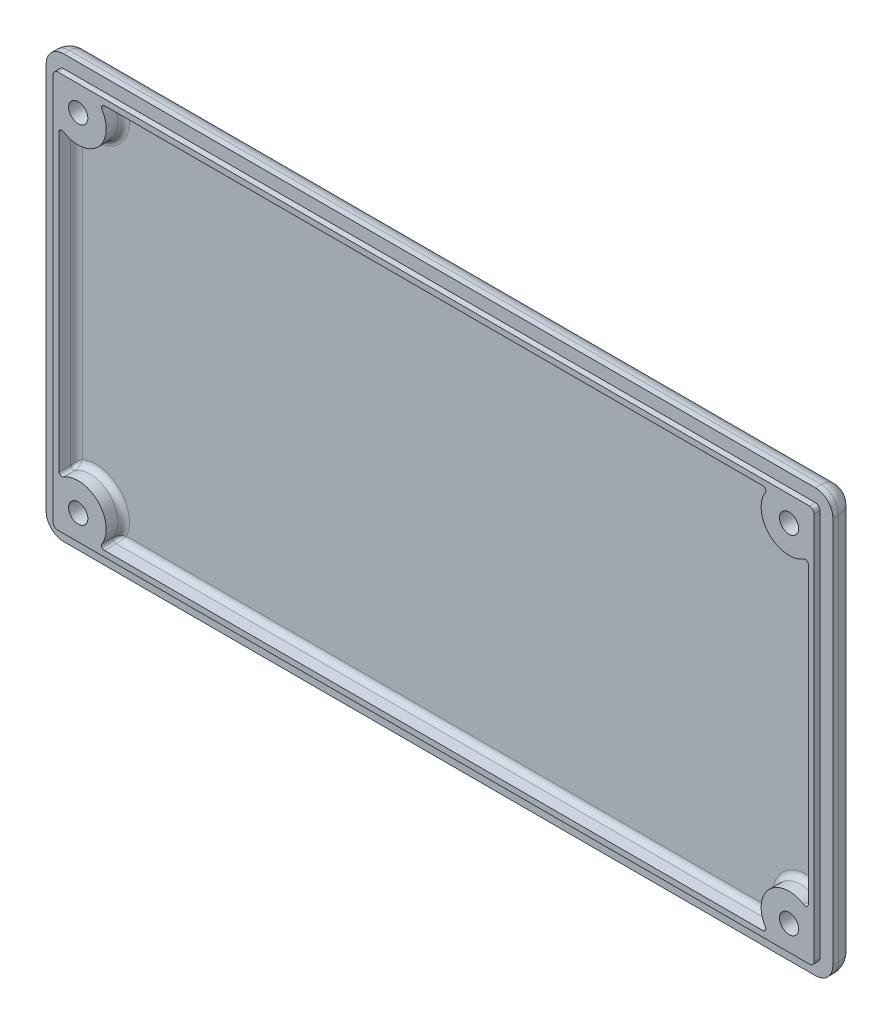
SolidWorks part; units mm, degrees
ref_plane "Front Plane" through (0, 0, 0) normal (0, 0, 1) x (1, 0, 0)
ref_plane "Top Plane" through (0, 0, 0) normal (0, 1, 0) x (1, 0, 0)
ref_plane "Right Plane" through (0, 0, 0) normal (1, 0, 0) x (0, 0, -1)
sketch "Sketch1" plane through (0, 0, 0) normal (0, 0, 1) x (1, 0, 0)
  line L0 (3, 0) -> (132, 0)
  line L1 (0, 3) -> (0, 69.5)
  line L2 (3, 72.5) -> (132, 72.5)
  line L3 (135, 3) -> (135, 69.5)
  arc A0 (132, 0) -> (135, 3) centre (132, 3) ccw
  arc A1 (132, 72.5) -> (135, 69.5) centre (132, 69.5) cw
  arc A2 (0, 69.5) -> (3, 72.5) centre (3, 69.5) cw
  arc A3 (3, 0) -> (0, 3) centre (3, 3) cw
  circle A4 centre (6.5, 66) radius 1.65
  circle A5 centre (128.5, 6.5) radius 1.65
  circle A6 centre (128.5, 66) radius 1.65
  circle A7 centre (6.5, 6.5) radius 1.65
extrude "Boss-Extrude1" add sketch "Sketch1" along normal blind 5
sketch "Sketch2" plane through (0, 0, 5) normal (0, 0, 1) x (1, 0, 0)
  line L0 (3, 72.5) -> (132, 72.5)
  line L9 (135, 69.5) -> (135, 3)
  line L12 (3, 70.3) -> (132, 70.3)
  line L13 (132, 0) -> (3, 0)
  line L15 (2.2, 69.5) -> (2.2, 3)
  line L16 (3, 2.2) -> (132, 2.2)
  line L17 (132.8, 69.5) -> (132.8, 3)
  line L19 (0, 3) -> (0, 69.5)
  arc A4 (132, 2.2) -> (132.8, 3) centre (132, 3) ccw
  arc A5 (132, 70.3) -> (132.8, 69.5) centre (132, 69.5) cw
  arc A6 (2.2, 3) -> (3, 2.2) centre (3, 3) ccw
  arc A7 (3, 70.3) -> (2.2, 69.5) centre (3, 69.5) ccw
  arc A8 (3, 72.5) -> (0, 69.5) centre (3, 69.5) ccw
  arc A9 (132, 72.5) -> (135, 69.5) centre (132, 69.5) cw
  arc A10 (135, 3) -> (132, 0) centre (132, 3) cw
  arc A11 (0, 3) -> (3, 0) centre (3, 3) ccw
extrude "Cut-Extrude1" cut sketch "Sketch2" against normal blind 1
fillet "Fillet1" radius 3 8 edges at (134.1213, 71.6213, 0) (135, 36.25, 0) (134.1213, 0.8787, 0) (67.5, 0, 0) (0.8787, 0.8787, 0) (0, 36.25, 0) (0.8787, 71.6213, 0) (67.5, 72.5, 0)
sketch "Sketch3" plane through (0, 0, 5) normal (0, 0, 1) x (1, 0, 0)
  line L9 (11, 69.3) -> (124, 69.3)
  line L10 (3.2, 61.5) -> (3.2, 11)
  line L11 (11, 3.2) -> (124, 3.2)
  line L12 (131.8, 61.5) -> (131.8, 11)
  arc A0 (3.9642, 61.9245) -> (10.5755, 68.5358) centre (6.5, 66) ccw
  arc A1 (10.5755, 3.9642) -> (3.9642, 10.5755) centre (6.5, 6.5) ccw
  arc A2 (124.4245, 68.5358) -> (131.0358, 61.9245) centre (128.5, 66) ccw
  arc A3 (131.0358, 10.5755) -> (124.4245, 3.9642) centre (128.5, 6.5) ccw
  arc A4 (131.8, 11) -> (131.0358, 10.5755) centre (131.3, 11) cw
  arc A5 (124.4245, 3.9642) -> (124, 3.2) centre (124, 3.7) cw
  arc A6 (131.0358, 61.9245) -> (131.8, 61.5) centre (131.3, 61.5) cw
  arc A7 (124, 69.3) -> (124.4245, 68.5358) centre (124, 68.8) cw
  arc A8 (10.5755, 68.5358) -> (11, 69.3) centre (11, 68.8) cw
  arc A9 (3.9642, 61.9245) -> (3.2, 61.5) centre (3.7, 61.5) ccw
  arc A10 (10.5755, 3.9642) -> (11, 3.2) centre (11, 3.7) ccw
  arc A11 (3.9642, 10.5755) -> (3.2, 11) centre (3.7, 11) cw
extrude "Cut-Extrude2" cut sketch "Sketch3" against normal offset from surface (3 mm away) 2 up to face at (67.5, 36.25, 0)
fillet "Fillet2" radius 1 16 edges at (3.4572, 10.5629, 2) (9.8941, 9.8941, 2) (10.5629, 3.4572, 2) (67.5, 3.2, 2) (124.4371, 3.4572, 2) (125.1059, 9.8941, 2) (131.5428, 10.5629, 2) (131.8, 36.25, 2) (131.5428, 61.9371, 2) (125.1059, 62.6059, 2) (124.4371, 69.0428, 2) (67.5, 69.3, 2) (10.5629, 69.0428, 2) (9.8941, 62.6059, 2) (3.4572, 61.9371, 2) (3.2, 36.25, 2)
sketch "Sketch4" plane through (0, 0, 0) normal (0, 0, -1) x (-1, 0, 0)
  circle A0 centre (-128.5, 66) radius 3
  circle A1 centre (-128.5, 6.5) radius 3
  circle A2 centre (-6.5, 66) radius 3
  circle A3 centre (-6.5, 6.5) radius 3
extrude "Cut-Extrude3" cut sketch "Sketch4" against normal offset from surface (2 mm away) 3 up to face at (67.5, 36.25, 5)
